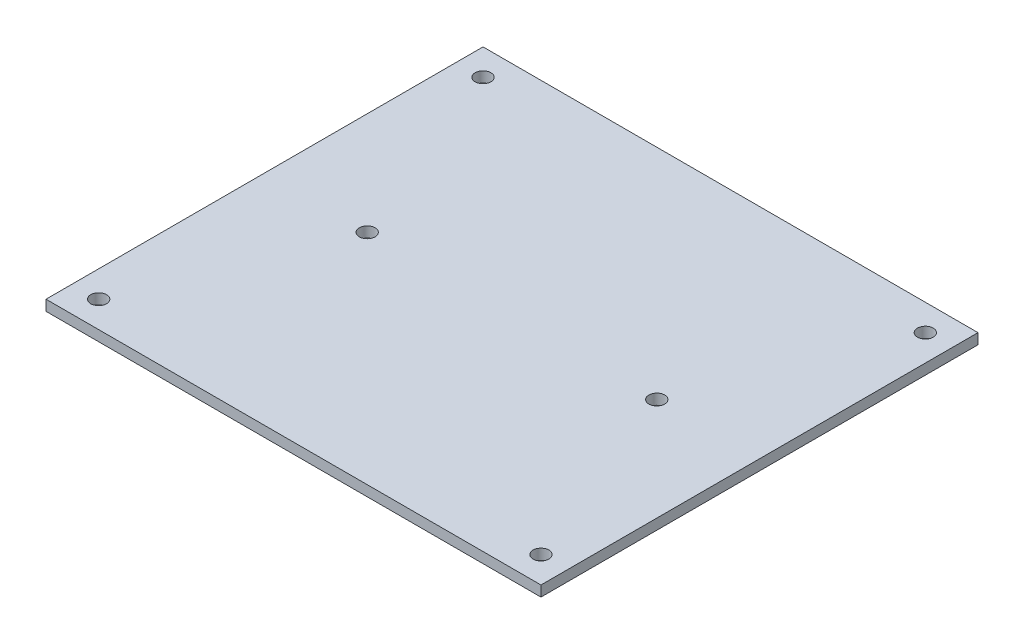
SolidWorks part; units mm, degrees
ref_plane "Front Plane" through (0, 0, 0) normal (0, 0, 1) x (1, 0, 0)
ref_plane "Top Plane" through (0, 0, 0) normal (0, 1, 0) x (1, 0, 0)
ref_plane "Right Plane" through (0, 0, 0) normal (1, 0, 0) x (0, 0, -1)
sketch "Sketch1" plane through (0, 0, 0) normal (0, 1, 0) x (1, 0, 0)
  line L1 (-47, -41.5) -> (47, -41.5)
  line L2 (-47, -41.5) -> (-47, 41.5)
  line L3 (-47, 41.5) -> (47, 41.5)
  line L4 (47, -41.5) -> (47, 41.5)
  line L5 (-47, -41.5) -> (47, 41.5) construction
  line L6 (-47, 41.5) -> (47, -41.5) construction
  line L7 (-42, -36.5) -> (42, -36.5) construction
  line L8 (-42, -36.5) -> (-42, 36.5) construction
  line L9 (-42, 36.5) -> (42, 36.5) construction
  line L10 (42, -36.5) -> (42, 36.5) construction
  line L11 (-42, -36.5) -> (42, 36.5) construction
  line L12 (-42, 36.5) -> (42, -36.5) construction
  circle A0 centre (-42, 36.5) radius 1.5
  circle A1 centre (42, 36.5) radius 1.5
  circle A2 centre (42, -36.5) radius 1.5
  circle A3 centre (-42, -36.5) radius 1.5
  point P0 (0, 0)
  point P14 (0, 0)
  dimension "D3" = 3
  dimension "D1" = 83
  dimension "D2" = 94
  dimension "D4" = 5
  dimension "D5" = 5
extrude "Boss-Extrude1" add sketch "Sketch1" along normal blind 2
sketch "Sketch2" plane through (0, 2, 0) normal (0, 1, 0) x (1, 0, 0)
  line L0 (0, 41.5) -> (0, -41.5) construction
  line L1 (47, 41.5) -> (-47, 41.5) construction
  line L2 (-47, -41.5) -> (47, -41.5) construction
  circle A0 centre (27.5, 0) radius 1.5
  circle A1 centre (-27.5, 0) radius 1.5
  dimension "D1" = 3
  dimension "D2" = 27.5
  dimension "D3" = 41.5
extrude "Cut-Extrude1" cut sketch "Sketch2" against normal through all
equation "\"D5@Sketch1\"=\"D4@Sketch1\""
